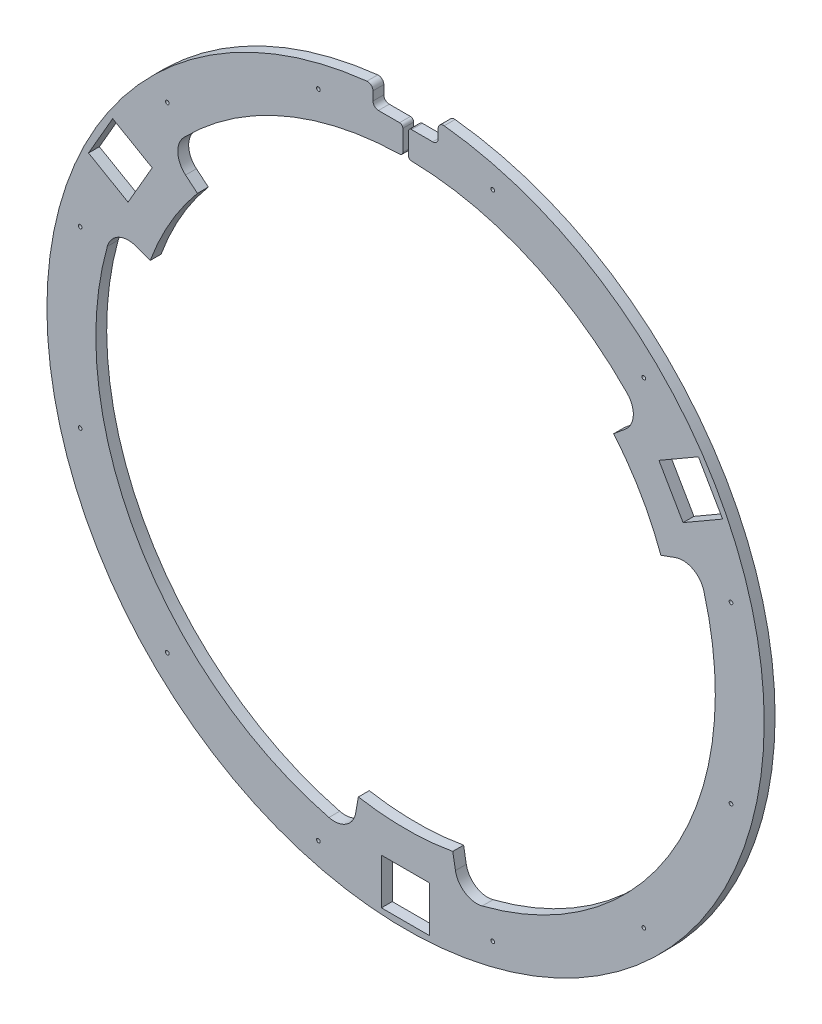
SolidWorks part; units mm, degrees
ref_plane "Front Plane" through (0, 0, 0) normal (0, 0, 1) x (1, 0, 0)
ref_plane "Top Plane" through (0, 0, 0) normal (0, 1, 0) x (1, 0, 0)
ref_plane "Right Plane" through (0, 0, 0) normal (1, 0, 0) x (0, 0, -1)
sketch "Sketch2" plane through (0, 0, -520.3606) normal (0, 0, 1) x (1, 0, 0)
  line L0 (0, 0) -> (0, 142.2716) construction
  line L1 (244.2192, 141) -> (0, 0) construction
  line L2 (22.225, -324) -> (22.225, -282)
  line L3 (22.225, -282) -> (-22.225, -282)
  line L4 (269.4797, 181.2474) -> (233.1067, 160.2474)
  line L5 (233.1067, 160.2474) -> (255.3317, 121.7526)
  line L6 (255.3317, 121.7526) -> (291.7047, 142.7526)
  line L7 (291.7047, 142.7526) -> (269.4797, 181.2474)
  line L8 (-22.225, -282) -> (-22.225, -324)
  line L9 (-22.225, -324) -> (22.225, -324)
  line L10 (-291.7047, 142.7526) -> (-255.3317, 121.7526)
  line L11 (-255.3317, 121.7526) -> (-233.1067, 160.2474)
  line L12 (-233.1067, 160.2474) -> (-269.4797, 181.2474)
  line L13 (-269.4797, 181.2474) -> (-291.7047, 142.7526)
  circle A0 centre (0, 0) radius 330
  circle A2 centre (0, 0) radius 250
  point P15 (0, 0)
  point P37 (-7.2575, -45.052)
  dimension "D1" = 660
  dimension "D6" = 500
  dimension "D2" = 42
  dimension "D3" = 44.45
  dimension "D4" = 282
  dimension "D5" = 60
  dimension "D7" = 3
extrude "Boss-Extrude1" add sketch "Sketch2" along normal blind 10
sketch "Sketch3" plane through (0, 0, -510.3606) normal (0, 0, 1) x (1, 0, 0)
  line L0 (191.5111, 160.6969) -> (202.4228, 169.8529)
  line L1 (-191.5111, 160.6969) -> (-202.4228, 169.8529)
  line L2 (43.412, -246.2019) -> (45.8855, -260.2297)
  line L4 (234.9232, 85.505) -> (248.3083, 90.3768)
  line L6 (0, 0) -> (0, 240.4153) construction
  line L7 (191.5111, 160.6969) -> (0, 0) construction
  line L8 (-234.9232, 85.505) -> (-248.3083, 90.3768)
  line L9 (-43.412, -246.2019) -> (-45.8855, -260.2297)
  arc A0 (203.874, 199.1492) -> (-203.874, 199.1492) centre (0, 0) ccw
  circle A1 centre (0, 0) radius 250 construction
  arc A2 (191.5111, 160.6969) -> (-191.5111, 160.6969) centre (0, 0) ccw
  arc A3 (-202.4228, 169.8529) -> (-203.874, 199.1492) centre (-189.5671, 185.1738) cw
  arc A4 (202.4228, 169.8529) -> (203.874, 199.1492) centre (189.5671, 185.1738) ccw
  circle A5 centre (0, 0) radius 330 construction
  arc A6 (70.5312, -276.1346) -> (274.4052, 76.9855) centre (0, 0) ccw
  arc A7 (43.412, -246.2019) -> (234.9232, 85.505) centre (0, 0) ccw
  arc A8 (248.3083, 90.3768) -> (274.4052, 76.9855) centre (255.1487, 71.583) cw
  arc A9 (45.8855, -260.2297) -> (70.5312, -276.1346) centre (65.5817, -256.7568) ccw
  arc A10 (-274.4052, 76.9855) -> (-70.5312, -276.1346) centre (0, 0) ccw
  arc A11 (-234.9232, 85.505) -> (-43.412, -246.2019) centre (0, 0) ccw
  arc A12 (-45.8855, -260.2297) -> (-70.5312, -276.1346) centre (-65.5817, -256.7568) cw
  arc A13 (-248.3083, 90.3768) -> (-274.4052, 76.9855) centre (-255.1487, 71.583) ccw
  point P33 (0, 0)
  dimension "D1" = 45
  dimension "D3" = 20
  dimension "D2" = 100
  dimension "D4" = 3
extrude "Cut-Extrude1" cut sketch "Sketch3" against normal blind 10
sketch "Sketch5" plane through (0, 0, -510.3606) normal (0, 0, 1) x (1, 0, 0)
  line L0 (0, 0) -> (0, 370) construction
  line L1 (30, 370) -> (30, 310)
  line L2 (30, 370) -> (-30, 370)
  line L4 (30, 310) -> (-30, 310)
  line L5 (-30, 370) -> (-30, 310)
  dimension "D1" = 310
  dimension "D2" = 60
  dimension "D3" = 60
extrude "Cut-Extrude2" cut sketch "Sketch5" against normal blind 10
fillet "Fillet1" radius 5 4 edges at (30, 310, -515.3606) (30, 328.6335, -515.3606) (-30, 328.6335, -515.3606) (-30, 310, -515.3606)
sketch "Sketch6" plane through (0, 0, -510.3606) normal (0, 0, 1) x (1, 0, 0)
  line L0 (0, 0) -> (0, 347.7499) construction
  line L2 (-2.5, 310) -> (2.5, 310)
  line L3 (-25, 310) -> (25, 310) construction
  line L4 (-2.5, 280) -> (2.5, 280)
  line L5 (2.5, 310) -> (2.5, 280)
  line L6 (-2.5, 310) -> (-2.5, 280)
  dimension "D1" = 5
  dimension "D2" = 30
extrude "Cut-Extrude3" cut sketch "Sketch6" against normal blind 10
fillet "Fillet2" radius 3 4 edges at (-2.5, 310, -515.3606) (2.5, 310, -515.3606) (-2.5, 284.989, -515.3606) (2.5, 284.989, -515.3606)
hole_wizard "CSK for M3 Flat Head Machine Screw1" positions "Sketch7" profile "Sketch8" countersink size "M3" standard "ANSI Metric" end condition through all
sketch "Sketch7" plane through (0, 0, -530.3606) normal (0, 0, -1) x (1, 0, 0)
  line L0 (80.2339, 299.437) -> (0, 0) construction
  line L2 (0, 0) -> (0, 423.7069) construction
  circle A0 centre (0, 0) radius 310 construction
  point P0 (80.2339, 299.437)
  point P21 (219.2031, 219.2031)
  point P22 (299.437, 80.2339)
  point P23 (299.437, -80.2339)
  point P24 (219.2031, -219.2031)
  point P25 (80.2339, -299.437)
  point P26 (-80.2339, -299.437)
  point P27 (-219.2031, -219.2031)
  point P28 (-299.437, -80.2339)
  point P29 (-299.437, 80.2339)
  point P30 (-219.2031, 219.2031)
  point P31 (-80.2339, 299.437)
  point P32 (0, 0)
sketch "Sketch8" plane through (80.2339, -299.437, -530.3606) normal (1, 0, 0) x (0, 1, 0)
  line L0 (0, 0) -> (0, 20)
  line L1 (0, 20) -> (1.7, 20)
  line L2 (1.7, 20) -> (1.7, 1.45)
  line L3 (1.7, 1.45) -> (3.15, 0)
  line L4 (3.15, 0) -> (0, 0)
  line L5 (-1.7, 1.45) -> (-3.15, 0) construction
  line L6 (0, -6.35) -> (0, 107.95) construction
  dimension "Thru Hole Dia." = 3.4
  dimension "Thru Hole Depth" = 20
  dimension "Near C'Sink Dia." = 6.3
  dimension "Near C'Sink Angle" = 90
